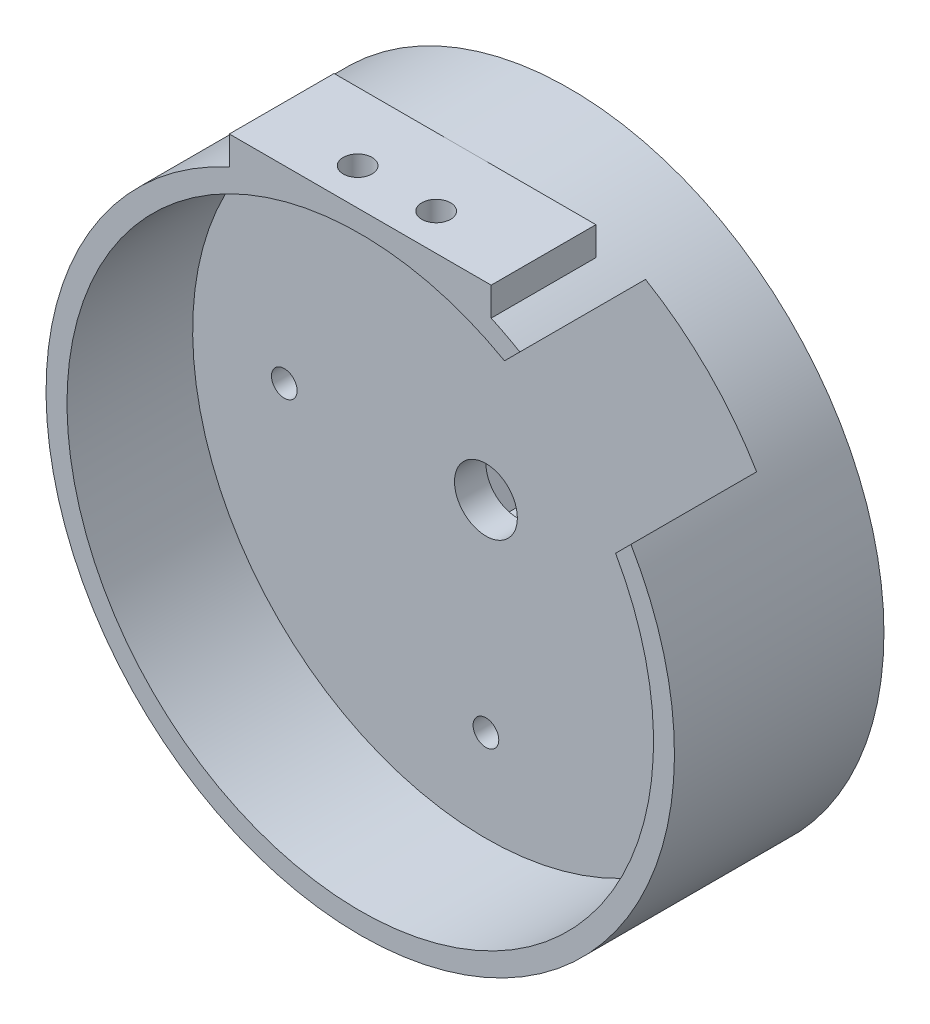
SolidWorks part; units mm, degrees
ref_plane "前视基准面" through (0, 0, 0) normal (0, 0, 1) x (1, 0, 0)
ref_plane "上视基准面" through (0, 0, 0) normal (0, 1, 0) x (1, 0, 0)
ref_plane "右视基准面" through (0, 0, 0) normal (1, 0, 0) x (0, 0, -1)
other "Configuration Table"
sketch "草图1" plane through (0, 0, 0) normal (0, 0, 1) x (1, 0, 0)
  circle A0 centre (0, 0) radius 30
  dimension "D1" = 60
extrude "凸台-拉伸1" add sketch "草图1" along normal blind 25
sketch "草图2" plane through (0, 0, 0) normal (0, 0, -1) x (-1, 0, 0)
  line L0 (0, 0) -> (0, 30) construction
  line L1 (-12.5, 30) -> (12.5, 30)
  line L2 (12.5, 30) -> (12.5, 27.2718)
  line L3 (-12.5, 30) -> (-12.5, 27.2718)
  circle A0 centre (0, 0) radius 30 construction
  arc A1 (-12.5, 27.2718) -> (0, 30) centre (0, 0) cw
  arc A2 (12.5, 27.2718) -> (0, 30) centre (0, 0) cw
  arc A3 (12.5, 27.2718) -> (0, 30) centre (0, 0) ccw
  circle M4 centre (0, 0) radius 30
  dimension "D1" = 12.5
extrude "凸台-拉伸2" add sketch "草图2" against normal blind 10 contours L2 L1 M4 | L1 L3 M4 region at (9.4041, 29.1883, 0) region at (-9.4041, 29.1883, 0)
sketch "草图3" plane through (0, 0, 10) normal (0, 0, 1) x (1, 0, 0)
  line L0 (-12.5, 27.2718) -> (-12.5, 30)
  line L1 (-12.5, 30) -> (12.5, 30)
  line L2 (12.5, 30) -> (12.5, 27.2718)
  arc A0 (-12.5, 27.2718) -> (0, 30) centre (0, 0) ccw
  arc A1 (0, 30) -> (12.3929, 27.3206) centre (0, 0) cw
  line M1 (-12.5, 30) -> (-12.5, 27.2718)
  arc M2 (-12.5, 27.2718) -> (0, 30) centre (0, 0) cw
  line M3 (0, 30) -> (-12.5, 30)
extrude "凸台-拉伸3" add sketch "草图3" along normal blind 10 contours M3 M1 M2 | A0 L2 L1 region at (-9.4041, 29.1883, 10) region at (9.4041, 29.1883, 10)
sketch "草图4" plane through (0, 0, 0) normal (0, 0, -1) x (-1, 0, 0)
  line L0 (-12.5, 27.2718) -> (-12.5, 30)
  line L1 (-12.5, 30) -> (12.5, 30)
  line L2 (12.5, 30) -> (12.5, 27.2718)
  arc A0 (-12.5, 27.2718) -> (0, 30) centre (0, 0) ccw
  arc A1 (12.5, 27.2718) -> (0, 30) centre (0, 0) ccw
  arc A2 (-12.5, 27.2718) -> (0, 30) centre (0, 0) cw
  line M2 (12.5, 27.2718) -> (12.5, 30)
  line M3 (12.5, 30) -> (-12.5, 30)
  line M4 (-12.5, 30) -> (-12.5, 27.2718)
extrude "切除-拉伸1" cut sketch "草图4" against normal blind 10 contours A2 L1 M4 | A0 M2 M3 region at (9.4041, 29.1883, 0) region at (-9.4041, 29.1883, 0)
sketch "草图5" plane through (0, 30, 0) normal (0, 1, 0) x (1, 0, 0)
  line L0 (-12.5, -13) -> (12.5, -13)
  line L1 (-12.5, -20) -> (-12.5, -10) construction
  line L2 (12.5, -20) -> (12.5, -10) construction
  line L3 (0, -10) -> (0, -20) construction
  line L4 (-12.5, -10) -> (0, -10) construction
  line L5 (-7.5, -10) -> (-7.5, -20)
  line L6 (0, -20) -> (-12.5, -20) construction
  line L7 (7.5, -10) -> (7.5, -20)
  line L8 (-3.75, -10) -> (-3.75, -20) construction
  line L9 (3.75, -10) -> (3.75, -20) construction
  line L10 (-7.5, -16.5) -> (7.5, -16.5) construction
  circle A0 centre (-3.75, -16.5) radius 1.375
  circle A1 centre (3.75, -16.5) radius 1.375
  dimension "D1" = 3
  dimension "D5" = 2.75
  dimension "D2" = 5
  dimension "D3" = 3.75
  dimension "D4" = 3.5
extrude "切除-拉伸2" cut sketch "草图5" against normal blind 3 contours A0 | A1 region at (-3.75, 30, 16.5) region at (3.75, 30, 16.5)
sketch "草图7" plane through (0, 0, 25) normal (0, 0, 1) x (1, 0, 0)
  circle A0 centre (0, 0) radius 28
  point P3 (15.9764, -10.713)
  dimension "D1" = 56
extrude "切除-拉伸4" cut sketch "草图7" against normal blind 17
sketch "草图8" plane through (0, 0, 0) normal (0, 0, -1) x (-1, 0, 0)
  circle A0 centre (0, 0) radius 19.25 construction
  circle A1 centre (0, 19.25) radius 1.225
  circle A2 centre (19.25, 0) radius 1.225
  circle A3 centre (0, -19.25) radius 1.225
  circle A4 centre (-19.25, 0) radius 1.225
  point P14 (0, 0)
  dimension "D1" = 38.5
  dimension "D3" = 2.45
  dimension "D2" = 4
extrude "切除-拉伸5" cut sketch "草图8" against normal blind 22 contours A3 | A4 | A1 | A2 region at (0, 19.25, 0) region at (0, -19.25, 0) region at (19.25, 0, 0)
sketch "草图9" plane through (0, 0, 0) normal (0, 0, -1) x (-1, 0, 0)
  point P0 (0, 0)
ref_axis "基准轴1" through (0, 0, 0) along (0, 0, -1)
sketch "草图10" plane through (0, 0, 0) normal (0, 0, -1) x (-1, 0, 0)
  circle A0 centre (0, 0) radius 3
  dimension "D1" = 6
extrude "切除-拉伸6" cut sketch "草图10" against normal through all contours A0 region at (0, 0, 0)
sketch "草图11" plane through (0, 0, 0) normal (0, 0, -1) x (-1, 0, 0)
  circle A0 centre (0, 19.25) radius 2.25
  point P12 (0.375, -0.375)
  dimension "D1" = 4.5
sketch "草图13" plane through (0, 0, 25) normal (0, 0, 1) x (1, 0, 0)
  line L0 (19.25, 0) -> (0, 19.25) construction
  line L1 (0, 19.25) -> (0, 0) construction
  line L2 (0, 0) -> (19.25, 0) construction
  line L3 (0, 0) -> (21.2132, 21.2132) construction
  line L4 (14.9283, 4.3217) -> (25.8429, 15.2363)
  line L5 (4.3217, 14.9283) -> (15.2363, 25.8429)
  line L6 (4.3217, 14.9283) -> (14.9283, 4.3217)
  circle A0 centre (0, 0) radius 30 construction
  arc A1 (15.2363, 25.8429) -> (25.8429, 15.2363) centre (0, 0) cw
  point P9 (9.625, 9.625)
  dimension "D1" = 7.5
  dimension "D2" = 45
extrude "切除-拉伸8" cut sketch "草图13" against normal blind 17
sketch "草图14" plane through (0, 0, 25) normal (0, 0, 1) x (1, 0, 0)
  circle A0 centre (0, 0) radius 30
extrude "切除-拉伸9" cut sketch "草图14" against normal blind 5
extrude "切除-拉伸10" cut sketch "草图11" against normal blind 2.5
pattern_circular "阵列(圆周)1" count 4 over 360 about axis through (0, 0, 0) along (0, 0, -1) of "切除-拉伸10"
sketch "草图17" plane through (0, 0, 0) normal (0, 0, -1) x (-1, 0, 0)
  line L1 (5.77, 0) -> (2.885, 4.997)
  line L2 (2.885, 4.997) -> (-2.885, 4.997)
  line L3 (-2.885, 4.997) -> (-5.77, 0)
  line L4 (-5.77, 0) -> (-2.885, -4.997)
  line L5 (-2.885, -4.997) -> (2.885, -4.997)
  line L6 (2.885, -4.997) -> (5.77, 0)
  circle A0 centre (0, 0) radius 4.997 construction
  dimension "D1" = 5.77
extrude "切除-拉伸11" cut sketch "草图17" against normal blind 5
